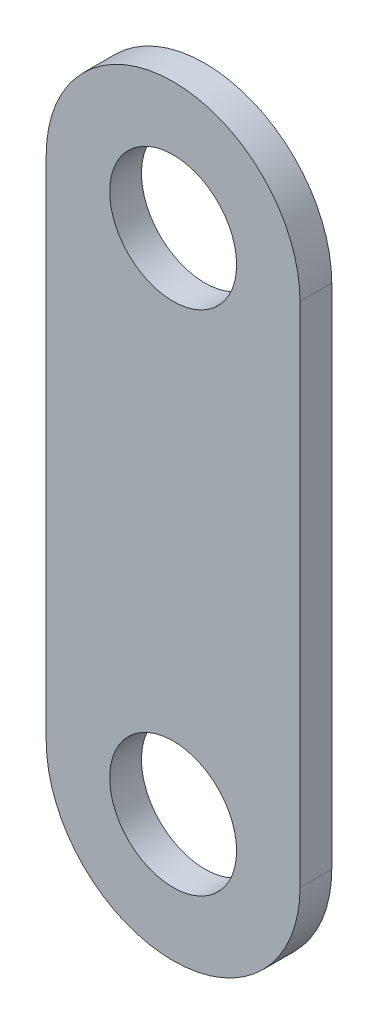
SolidWorks part; units mm, degrees
ref_plane "Front" through (0, 0, 0) normal (0, 0, 1) x (1, 0, 0)
ref_plane "Top" through (0, 0, 0) normal (0, 1, 0) x (1, 0, 0)
ref_plane "Right" through (0, 0, 0) normal (1, 0, 0) x (0, 0, -1)
sketch "Sketch1" plane through (0, 0, 0) normal (0, 0, 1) x (1, 0, 0)
  line L0 (-29.9132, -25.0577) -> (-29.9132, 25.7423)
  line L1 (-4.5132, 25.7423) -> (-4.5132, -25.0577)
  circle A0 centre (-17.2132, 25.7423) radius 12.7
  circle A1 centre (-17.2132, -25.0577) radius 12.7
  circle A2 centre (-17.2132, 25.7423) radius 6.35
  circle A3 centre (-17.2132, -25.0577) radius 6.35
  point P8 (-4.5132, 0.3423)
  dimension "D1" = 50.8
  dimension "D3" = 12.7
  dimension "D4" = 12.7
  dimension "D2" = 25.4
extrude "Boss-Extrude1" add sketch "Sketch1" along normal blind 3.175 contours A0 A2 | A1 L1 A0 L0 | A1 A3 region at (-17.2132, 0.3423, 0) region at (-17.2132, -12.7169, 0) region at (-17.2132, 38.0831, 0)
